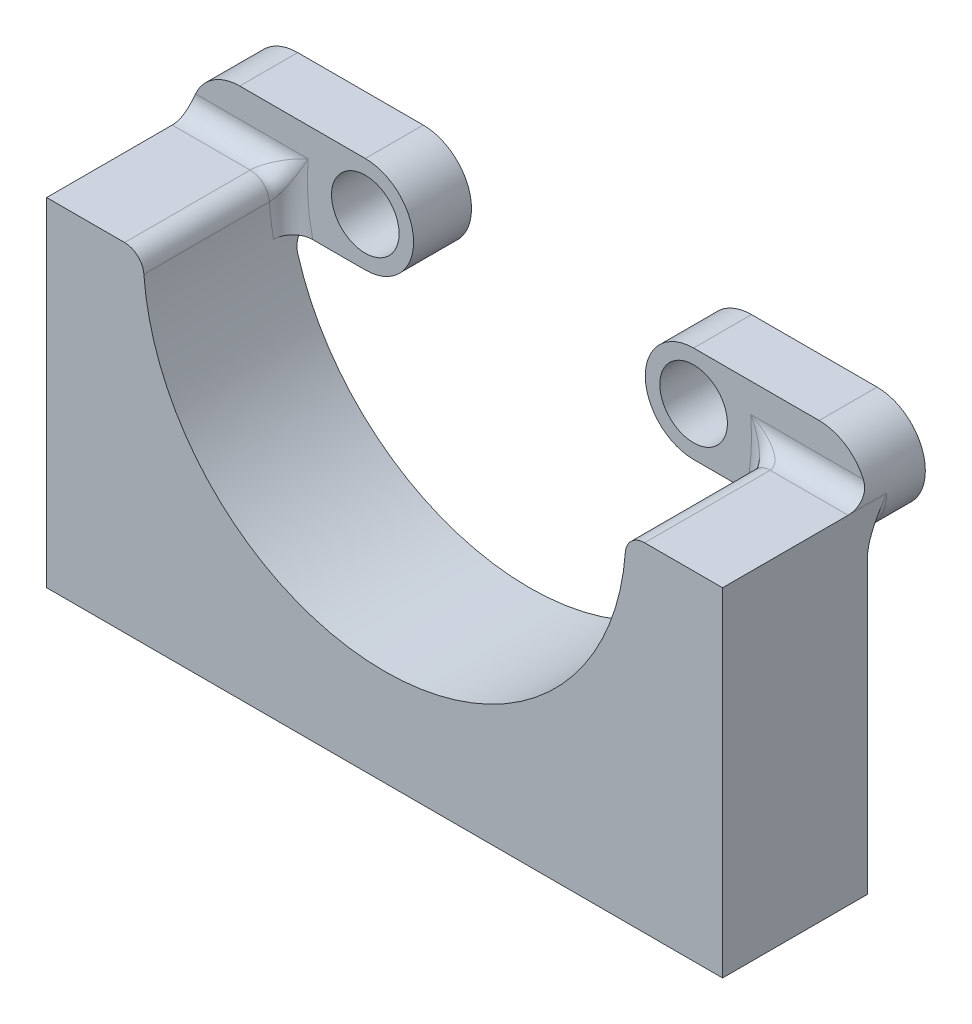
SolidWorks part; units mm, degrees
ref_plane "Front Plane" through (0, 0, 0) normal (0, 0, 1) x (1, 0, 0)
ref_plane "Top Plane" through (0, 0, 0) normal (0, 1, 0) x (1, 0, 0)
ref_plane "Right Plane" through (0, 0, 0) normal (1, 0, 0) x (0, 0, -1)
sketch "Sketch1" plane through (0, 0, 0) normal (0, 0, 1) x (1, 0, 0)
  line L0 (-17.5, 0) -> (17.5, 0)
  line L1 (17.5, 0) -> (17.5, 17.5)
  line L2 (17.5, 17.5) -> (12.5, 17.5)
  line L3 (-17.5, 0) -> (-17.5, 17.5)
  line L4 (-17.5, 17.5) -> (-12.5, 17.5)
  arc A0 (-12.5, 17.5) -> (12.5, 17.5) centre (0, 17.5) ccw
  point P4 (0, 0)
  point P11 (0, 5)
  dimension "D1" = 25
  dimension "D2" = 5
  dimension "D3" = 5
extrude "Boss-Extrude1" add sketch "Sketch1" along normal blind 7.5
sketch "Sketch2" plane through (0, 0, 0) normal (0, 0, -1) x (-1, 0, 0)
  line L0 (-12.5, 17.5) -> (12.5, 17.5) construction
  line L1 (-8.5, 17.5) -> (-15, 17.5) construction
  line L2 (-17.5, 17.5) -> (-12.5, 17.5) construction
  line L3 (-8.5, 15) -> (-15, 15)
  line L4 (-8.5, 20) -> (-15, 20)
  line L5 (0, 4.125) -> (0, -4.125) construction
  line L6 (8.5, 17.5) -> (15, 17.5) construction
  line L7 (8.5, 15) -> (15, 15)
  line L8 (8.5, 20) -> (15, 20)
  circle A0 centre (-8.5, 17.5) radius 1.75
  arc A1 (-8.5, 15) -> (-8.5, 20) centre (-8.5, 17.5) ccw
  arc A2 (-15, 20) -> (-15, 15) centre (-15, 17.5) ccw
  circle A3 centre (8.5, 17.5) radius 1.75
  arc A4 (8.5, 15) -> (8.5, 20) centre (8.5, 17.5) cw
  arc A5 (15, 20) -> (15, 15) centre (15, 17.5) cw
  point P6 (-11.75, 17.5)
  point P14 (-17.5, 17.5)
  point P21 (11.75, 17.5)
  dimension "D1" = 3.5
  dimension "D3" = 2.5
  dimension "D2" = 4
extrude "Boss-Extrude2" add sketch "Sketch2" along normal blind 3
fillet "Fillet1" radius 1 4 edges at (-13.6237, 15, 0) (-16.7678, 15.7322, 0) (16.7678, 15.7322, 0) (13.6237, 15, 0)
fillet "Fillet2" radius 1 2 edges at (-15, 17.5, 0) (15, 17.5, 0)
fillet "Fillet3" radius 1 2 edges at (12.477, 16.7425, 0) (-12.477, 16.7425, 0)
fillet "Fillet4" radius 1 4 edges at (12.5, 17.5, 4.25) (-12.5, 17.5, 4.25) (12.3714, 17.628, 0.5106) (-12.3714, 17.628, 0.5106)
